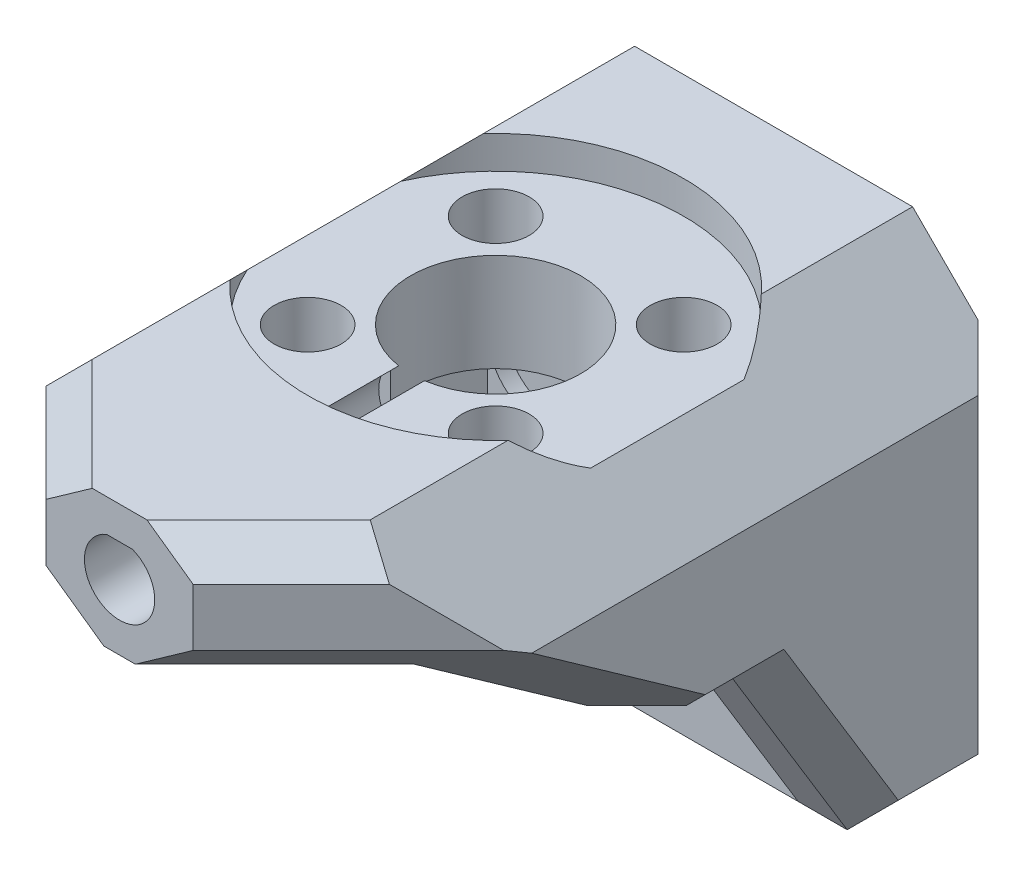
SolidWorks part; units mm, degrees
ref_plane "Front Plane" through (0, 0, 0) normal (0, 0, 1) x (1, 0, 0)
ref_plane "Top Plane" through (0, 0, 0) normal (0, 1, 0) x (1, 0, 0)
ref_plane "Right Plane" through (0, 0, 0) normal (1, 0, 0) x (0, 0, -1)
sketch "Sketch1" plane through (0, 0, 0) normal (0, 0, 1) x (1, 0, 0)
  line L1 (-13, 11.5) -> (13, 11.5)
  line L2 (-13, 11.5) -> (-13, -11.5)
  line L3 (-13, -11.5) -> (13, -11.5)
  line L4 (13, 11.5) -> (13, -11.5)
  line L5 (-13, 11.5) -> (13, -11.5) construction
  line L6 (-13, -11.5) -> (13, 11.5) construction
  circle A0 centre (-6, 4) radius 1.05
  circle A1 centre (6, 4) radius 1.05
  circle A2 centre (-6, -4) radius 1.05
  circle A3 centre (6, -4) radius 1.05
  point P0 (0, 0)
  dimension "D3" = 2.1
  dimension "D1" = 23
  dimension "D2" = 26
  dimension "D4" = 12
  dimension "D5" = 8
  dimension "D6" = 4
  dimension "D7" = 6
extrude "Boss-Extrude1" add sketch "Sketch1" along normal blind 8
sketch "Sketch2" plane through (0, 0, 8) normal (0, 0, 1) x (1, 0, 0)
  circle A0 centre (-6, 4) radius 3.55
  circle A1 centre (6, 4) radius 3.55
  circle A2 centre (6, -4) radius 3.55
  circle A3 centre (-6, -4) radius 3.55
  dimension "D1" = 7.1
extrude "Cut-Extrude1" cut sketch "Sketch2" against normal blind 1
sketch "Sketch3" plane through (0, 0, 8) normal (0, 0, 1) x (1, 0, 0)
  line L0 (13, -11.5) -> (13, 11.5) construction
  line L1 (-13, 11.5) -> (13, 11.5)
  line L2 (-13, 11.5) -> (-13, 7.5)
  line L3 (-9.5, 7.5) -> (9.5, 7.5)
  line L4 (13, 11.5) -> (13, 7.5)
  line L5 (-13, -11.5) -> (13, -11.5) construction
  line L7 (13, 7.5) -> (13, -11.5)
  line L8 (13, -11.5) -> (9.5, -11.5)
  line L9 (9.5, 7.5) -> (9.5, -11.5)
  line L11 (-13, -11.5) -> (-9.5, -11.5)
  line L12 (-13, -11.5) -> (-13, 7.5)
  line L14 (-9.5, -11.5) -> (-9.5, 7.5)
  dimension "D1" = 4
  dimension "D2" = 3.5
  dimension "D3" = 3.5
  dimension "D4" = 4
extrude "Boss-Extrude2" add sketch "Sketch3" along normal blind 72
sketch "Sketch4" plane through (-13, 0, 0) normal (-1, 0, 0) x (0, 0, 1)
  line L4 (0, 11.5) -> (0, -11.5)
  line L5 (0, -11.5) -> (80, -11.5)
  line L6 (80, -11.5) -> (80, 11.5)
  line L7 (80, 11.5) -> (0, 11.5)
  line L8 (0, 11.5) -> (0, -11.5)
  line L9 (0, -11.5) -> (80, -11.5)
  line L10 (80, -11.5) -> (80, 11.5)
  line L11 (80, 11.5) -> (0, 11.5)
  dimension "D1" = 0
extrude "Boss-Extrude3" add sketch "Sketch4" along normal blind 1.5
sketch "Sketch5" plane through (13, 0, 0) normal (1, 0, 0) x (0, 0, -1)
  line L4 (0, -11.5) -> (0, 11.5)
  line L5 (0, 11.5) -> (-80, 11.5)
  line L6 (-80, 11.5) -> (-80, -11.5)
  line L7 (-80, -11.5) -> (0, -11.5)
  line L8 (0, -11.5) -> (0, 11.5)
  line L9 (0, 11.5) -> (-80, 11.5)
  line L10 (-80, 11.5) -> (-80, -11.5)
  line L11 (-80, -11.5) -> (0, -11.5)
  dimension "D1" = 0
extrude "Boss-Extrude4" add sketch "Sketch5" along normal blind 1.5
sketch "Sketch6" plane through (0, 11.5, 0) normal (0, 1, 0) x (1, 0, 0)
  line L4 (14.5, 0) -> (-14.5, 0)
  line L5 (-14.5, 0) -> (-14.5, -80)
  line L6 (-14.5, -80) -> (14.5, -80)
  line L7 (14.5, -80) -> (14.5, 0)
  line L8 (14.5, 0) -> (-14.5, 0)
  line L9 (-14.5, 0) -> (-14.5, -80)
  line L10 (-14.5, -80) -> (14.5, -80)
  line L11 (14.5, -80) -> (14.5, 0)
  dimension "D1" = 0
extrude "Boss-Extrude5" add sketch "Sketch6" along normal blind 2
sketch "Sketch7" plane through (14.5, 0, 0) normal (1, 0, 0) x (0, 0, -1)
  line L0 (-8, -11.5) -> (-15, 0)
  line L1 (-80, -11.5) -> (0, -11.5) construction
  line L2 (-15, 0) -> (-52, 0)
  line L3 (-52, 0) -> (-80, 7.5)
  line L4 (-80, 13.5) -> (-80, -11.5) construction
  line L5 (-80, 7.5) -> (-80, -11.5)
  line L6 (-80, -11.5) -> (-8, -11.5)
  dimension "D1" = 8
  dimension "D2" = 15
  dimension "D3" = 6
  dimension "D4" = 28
extrude "Cut-Extrude2" cut sketch "Sketch7" against normal through all
sketch "Sketch8" plane through (-14.5, 0, 0) normal (-1, 0, 0) x (0, 0, 1)
  line L1 (80, 13.5) -> (50, 13.5)
  line L2 (80, 13.5) -> (80, 17.5)
  line L3 (80, 17.5) -> (50, 17.5)
  line L4 (50, 13.5) -> (50, 17.5)
  dimension "D1" = 10
  dimension "D2" = 30
extrude "Boss-Extrude6" add sketch "Sketch8" against normal up to surface (29 mm away) up to face at (14.5, 1.6429, 33.5714)
sketch "Sketch9" plane through (0, 17.5, 0) normal (0, 1, 0) x (1, 0, 0)
  line L0 (-5, -80) -> (-14.5, -50)
  line L1 (14.5, -80) -> (-14.5, -80) construction
  line L2 (-14.5, -50) -> (-14.5, -80)
  line L3 (-14.5, -80) -> (-5, -80)
  line L4 (14.5, -50) -> (14.5, -80)
  line L5 (14.5, -80) -> (5, -80)
  line L6 (5, -80) -> (14.5, -50)
  dimension "D1" = 10
  dimension "D2" = 9.5
extrude "Cut-Extrude3" cut sketch "Sketch9" against normal through all
sketch "Sketch10" plane through (14.5, 0, 0) normal (1, 0, 0) x (0, 0, -1)
  line L1 (-50, 0) -> (-65.7895, 0)
  line L2 (-50, 0) -> (-50, 7.5)
  line L3 (-50, 7.5) -> (-65.7895, 7.5)
  line L4 (-65.7895, 0) -> (-65.7895, 7.5)
extrude "Cut-Extrude4" cut sketch "Sketch10" against normal through all
chamfer "Chamfer1" distance 7.5 distance2 15 1 edges at (12, 7.5, 50) first distance on face at (12, 3.75, 50)
chamfer "Chamfer2" distance 7.5 distance2 15 1 edges at (-12, 7.5, 50) first distance on face at (-12, 3.75, 50)
chamfer "Chamfer3" distance 10 distance2 4 1 edges at (0, 13.5, 50) first distance on face at (0, 13.5, 25)
sketch "Sketch12" plane through (0, 13.5, 0) normal (0, 1, 0) x (1, 0, 0)
  circle A0 centre (0, -17) radius 5.2
  dimension "D1" = 10.4
  dimension "D2" = 17
extrude "Cut-Extrude5" cut sketch "Sketch12" against normal through all
sketch "Sketch14" plane through (0, 13.5, 0) normal (0, 1, 0) x (1, 0, 0)
  circle A0 centre (5.75, -11.25) radius 2.05
  circle A1 centre (5.75, -22.75) radius 2.05
  circle A2 centre (-5.75, -22.75) radius 2.05
  circle A3 centre (-5.75, -11.25) radius 2.05
  circle A4 centre (0, -17) radius 5.2 construction
  dimension "D1" = 4.1
  dimension "D2" = 11.5
  dimension "D3" = 5.75
  dimension "D4" = 11.5
  dimension "D5" = 5.75
extrude "Cut-Extrude6" cut sketch "Sketch14" against normal blind 5
sketch "Sketch15" plane through (0, 0, 80) normal (0, 0, 1) x (1, 0, 0)
  circle A0 centre (0, 11.5) radius 2.15
  dimension "D1" = 4.3
  dimension "D2" = 4
extrude "Cut-Extrude8" cut sketch "Sketch15" against normal blind 58
sketch "Sketch21" plane through (0, 0, 80) normal (0, 0, 1) x (1, 0, 0)
  line L0 (14.5, 0) -> (14.5, 17.5) construction
  line L1 (-14.5, 17.5) -> (14.5, 17.5)
  line L2 (-14.5, 17.5) -> (-14.5, 15.5)
  line L3 (-14.5, 15.5) -> (14.5, 15.5)
  line L4 (14.5, 17.5) -> (14.5, 15.5)
  dimension "D1" = 2
extrude "Cut-Extrude9" cut sketch "Sketch21" against normal through all
sketch "Sketch22" plane through (0, 0, 0) normal (0, 0, -1) x (-1, 0, 0)
  line L1 (14.5, 13.5) -> (-14.5, 13.5)
  line L2 (14.5, 13.5) -> (14.5, 15.5)
  line L3 (14.5, 15.5) -> (-14.5, 15.5)
  line L4 (-14.5, 13.5) -> (-14.5, 15.5)
extrude "Boss-Extrude7" add sketch "Sketch22" against normal up to surface (40 mm away) up to face at (0, 14.1917, 41.7292)
sketch "Sketch23" plane through (0, 13.5, 0) normal (0, -1, 0) x (-1, 0, 0)
  circle A1 centre (5.75, -11.25) radius 2.05
  circle A3 centre (5.75, -11.25) radius 2.05
  dimension "D1" = 0
extrude "Cut-Extrude10" cut sketch "Sketch23" against normal through all
sketch "Sketch24" plane through (0, 15.5, 0) normal (0, 1, 0) x (1, 0, 0)
  circle A0 centre (0, -17) radius 11.5
  dimension "D1" = 23
extrude "Cut-Extrude11" cut sketch "Sketch24" against normal blind 2
chamfer "Chamfer4" distance 6 angle 45 2 edges at (-14.5, 15.5, 25) (14.5, 15.5, 25)
chamfer "Chamfer5" distance 2 angle 45 8 edges at (-12.125, 3.75, 57.5) (12.125, 3.75, 57.5) (14.5, 0, 32.5) (14.5, -5.75, 11.5) (14.5, -11.5, 4) (-14.5, -11.5, 4) (-14.5, -5.75, 11.5) (-14.5, 0, 32.5) first distance on face at (-10.8125, 3.75, 57.5) first distance on face at (10.8125, 3.75, 57.5) first distance on face at (12, 0, 32.5) first distance on face at (12, -5.75, 11.5) first distance on face at (0, -11.5, 5.3333) first distance on face at (-12, -5.75, 11.5) first distance on face at (-12, 0, 32.5)
chamfer "Chamfer6" distance 2 angle 45 2 edges at (14.5, 0, 0) (-14.5, 0, 0)
sketch "Sketch25" plane through (0, 15.5, 0) normal (0, 1, 0) x (1, 0, 0)
  line L0 (-14.5, -50) -> (-14.5, -2) construction
  line L1 (-14.5, -40) -> (17.7904, -40)
  line L2 (-14.5, -40) -> (-14.5, -83.8822)
  line L3 (-14.5, -83.8822) -> (17.7904, -83.8822)
  line L4 (17.7904, -40) -> (17.7904, -83.8822)
  dimension "D1" = 40
extrude "Cut-Extrude12" cut sketch "Sketch25" against normal through all
chamfer "Chamfer7" distance 10 angle 45 2 edges at (-14.5, 5.75, 40) (14.5, 5.75, 40)
chamfer "Chamfer8" distance 10 angle 45 2 edges at (11, 0, 33.5) (-11, 0, 33.5)
chamfer "Chamfer9" distance 2 angle 45 2 edges at (-6.5, 15.5, 38) (6.5, 15.5, 38)
